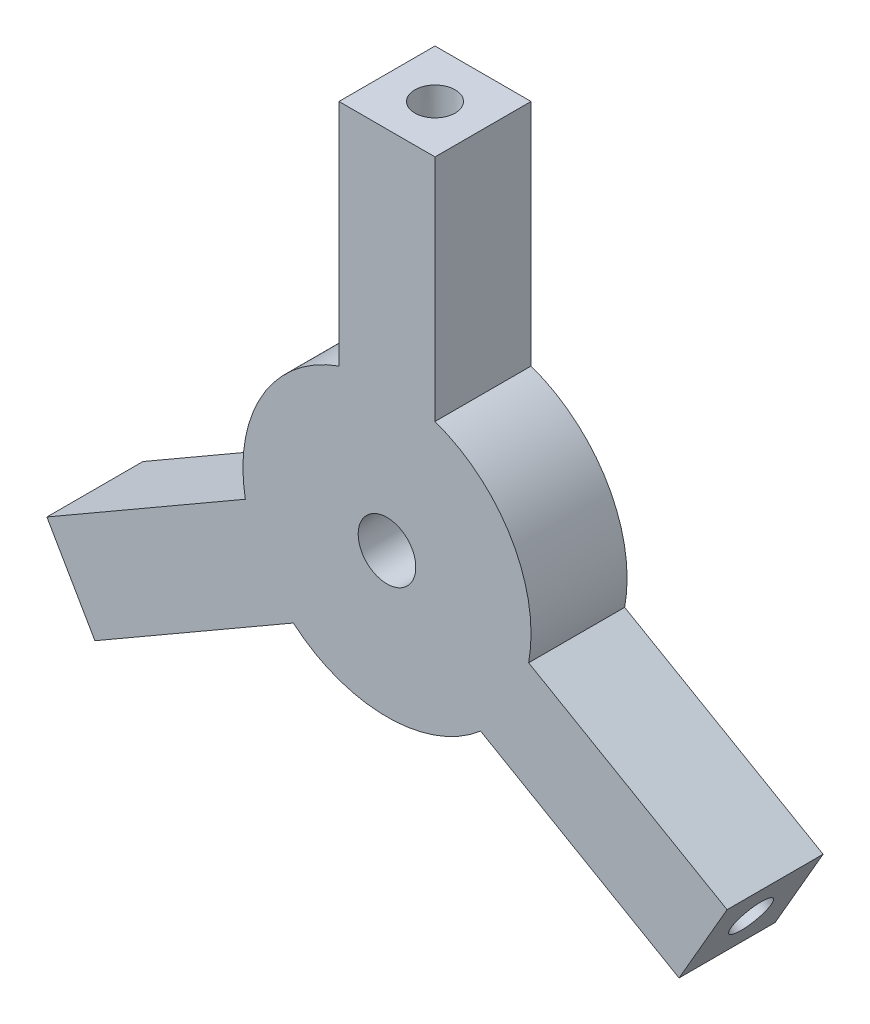
SolidWorks part; units mm, degrees
ref_plane "Front Plane" through (0, 0, 0) normal (0, 0, 1) x (1, 0, 0)
ref_plane "Top Plane" through (0, 0, 0) normal (0, 1, 0) x (1, 0, 0)
ref_plane "Right Plane" through (0, 0, 0) normal (1, 0, 0) x (0, 0, -1)
sketch "Sketch1" plane through (0, 0, 0) normal (0, 0, 1) x (1, 0, 0)
  line L5 (4.8737, -5.7006) -> (15.2045, -11.6651)
  line L6 (7.3737, -1.3705) -> (17.7045, -7.3349)
  line L7 (15.2045, -11.6651) -> (17.7045, -7.3349)
  line L9 (-7.3737, -1.3705) -> (-17.7045, -7.3349)
  line L10 (-4.8737, -5.7006) -> (-15.2045, -11.6651)
  line L11 (-17.7045, -7.3349) -> (-15.2045, -11.6651)
  line L13 (-2.5, 7.0711) -> (-2.5, 19)
  line L14 (2.5, 7.0711) -> (2.5, 19)
  line L15 (-2.5, 19) -> (2.5, 19)
  line L16 (-7.3737, -1.3705) -> (-2.5, 7.0711) construction
  line L17 (2.5, 7.0711) -> (7.3737, -1.3705) construction
  line L18 (-4.8737, -5.7006) -> (4.8737, -5.7006) construction
  line L19 (2.5, 19) -> (17.7045, -7.3349) construction
  line L20 (15.2045, -11.6651) -> (-15.2045, -11.6651) construction
  line L21 (-17.7045, -7.3349) -> (-2.5, 19) construction
  arc A0 (7.3737, -1.3705) -> (2.5, 7.0711) centre (0, 0) ccw
  arc A1 (-2.5, 7.0711) -> (-7.3737, -1.3705) centre (0, 0) ccw
  arc A2 (-4.8737, -5.7006) -> (4.8737, -5.7006) centre (0, 0) ccw
  point P1 (20.3445, -16.1457)
  dimension "D1" = 15
  dimension "D2" = 5
  dimension "D3" = 19
extrude "Boss-Extrude1" add sketch "Sketch1" along normal blind 5
sketch "Sketch2" plane through (0, 19, 0) normal (0, 1, 0) x (1, 0, 0)
  line L0 (0, 0) -> (0, -2.5) construction
  line L1 (0, -2.5) -> (2.5, -2.5) construction
  line L2 (2.5, -5) -> (2.5, 0) construction
  circle A0 centre (0, -2.5) radius 1.05
  dimension "D1" = 2.1
extrude "Cut-Extrude1" cut sketch "Sketch2" against normal blind 10
pattern_circular "CirPattern2" count 3 over 360 about axis through (0, 0, 5) along (0, 0, -1) of "Cut-Extrude1"
draft "Draft4" type of draft neutral plane draft angle 1 faces to draft 1 face at (0, 9, 3.55) neutral plane through (-2.5, 19, 5) neutral plane normal (0, 1, 0) parameters "D1"=1
draft "Draft5" type of draft neutral plane draft angle 1 faces to draft 1 face at (-7.7942, -4.5, 3.55) neutral plane through (-17.7045, -7.3349, 5) neutral plane normal (-0.866, -0.5, 0) parameters "D1"=1
draft "Draft6" type of draft neutral plane draft angle 1 faces to draft 1 face at (7.7942, -4.5, 3.55) neutral plane through (15.2045, -11.6651, 5) neutral plane normal (0.866, -0.5, 0) parameters "D1"=1
sketch "Sketch3" plane through (0, 0, 0) normal (0, 0, -1) x (-1, 0, 0)
  circle A0 centre (0, 0) radius 1.5
  dimension "D1" = 3
extrude "Cut-Extrude2" cut sketch "Sketch3" against normal through all
